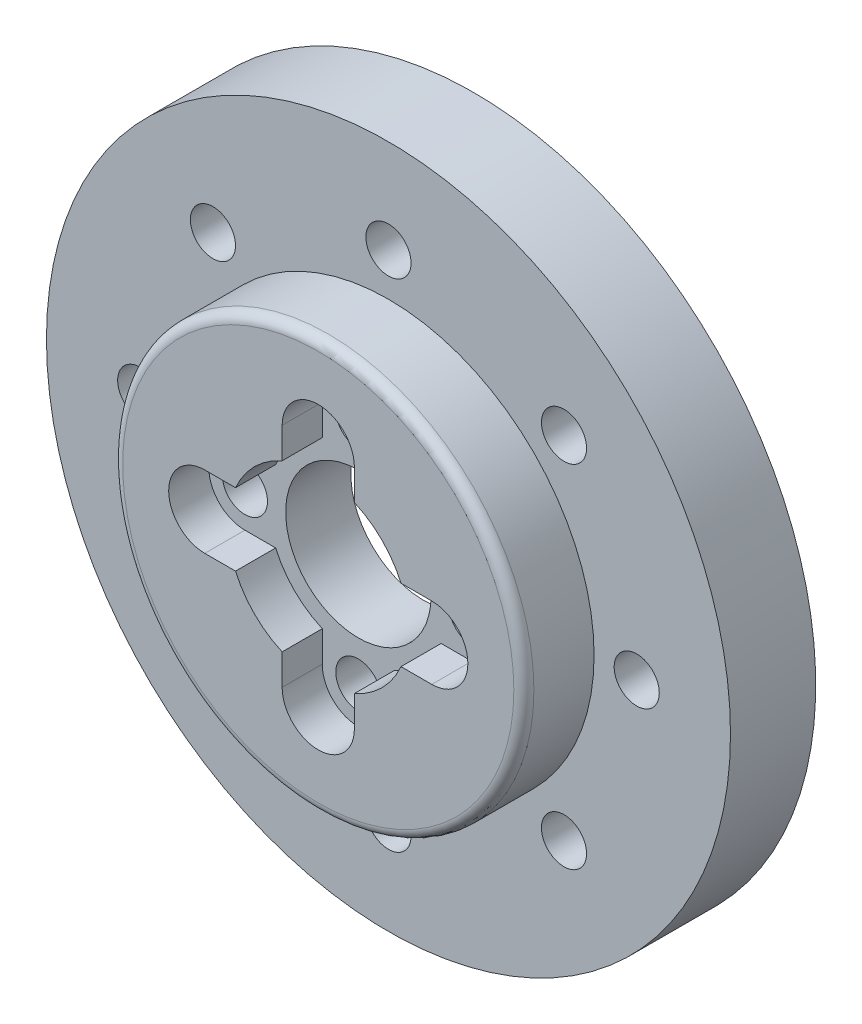
SolidWorks part; units mm, degrees
ref_plane "Front Plane" through (0, 0, 0) normal (0, 0, 1) x (1, 0, 0)
ref_plane "Top Plane" through (0, 0, 0) normal (0, 1, 0) x (1, 0, 0)
ref_plane "Right Plane" through (0, 0, 0) normal (1, 0, 0) x (0, 0, -1)
sketch "Sketch1" plane through (0, 0, 0) normal (0, 0, 1) x (1, 0, 0)
  circle A0 centre (0, 0) radius 34.1
  dimension "D1" = 68.2
extrude "Boss-Extrude1" add sketch "Sketch1" along normal mid plane 3.5
sketch "Sketch4" plane through (0, 0, 1.75) normal (0, 0, 1) x (1, 0, 0)
  circle A0 centre (0, 0) radius 28.5
  dimension "D1" = 57
extrude "Boss-Extrude2" add sketch "Sketch4" along normal blind 2
sketch "Sketch5" plane through (0, 0, -1.75) normal (0, 0, -1) x (-1, 0, 0)
  circle A0 centre (0, 0) radius 16.25
  circle A1 centre (0, 0) radius 34.1 construction
  circle A2 centre (0, 0) radius 34.1
  dimension "D1" = 32.5
extrude "Boss-Extrude3" add sketch "Sketch5" along normal blind 5
sketch "Sketch3" plane through (0, 0, 1.75) normal (0, 0, 1) x (1, 0, 0)
  circle A8 centre (0, 0) radius 11.3137 construction
  circle A9 centre (0, 11.3137) radius 2.25
  circle A11 centre (11.3137, 0) radius 2.25
  circle A13 centre (0, -11.3137) radius 2.25
  circle A15 centre (-11.3137, 0) radius 2.25
  point P21 (0, 0)
  dimension "D3" = 22.6274
  dimension "D4" = 4.5
  dimension "D5" = 4
extrude "Cut-Extrude2" cut sketch "Sketch3" against normal through all both and the other way through all
sketch "Sketch2" plane through (0, 0, 1.75) normal (0, 0, 1) x (1, 0, 0)
  circle A0 centre (0, 0) radius 7.25
  dimension "D1" = 14.5
extrude "Cut-Extrude1" cut sketch "Sketch2" along normal through all both and the other way through all
sketch "Sketch6" plane through (0, 0, 3.75) normal (0, 0, 1) x (1, 0, 0)
  circle A0 centre (0, 24.75) radius 2.25
  dimension "D1" = 4.5
  dimension "D2" = 24.75
extrude "Cut-Extrude3" cut sketch "Sketch6" against normal through all both and the other way through all
pattern_circular "CirPattern1" count 8 over 360 about axis through (0, 0, 1.75) along (0, 0, -1) of "Cut-Extrude3"
sketch "Sketch7" plane through (0, 0, 3.75) normal (0, 0, 1) x (1, 0, 0)
  circle A0 centre (0, 0) radius 20.5
  circle A5 centre (0, -11.3137) radius 2.25 construction
  circle A6 centre (11.3137, 0) radius 2.25 construction
  circle A7 centre (0, 11.3137) radius 2.25 construction
  circle A8 centre (-11.3137, 0) radius 2.25 construction
  circle A9 centre (0, 0) radius 7.25 construction
  circle A10 centre (0, -11.3137) radius 2.25
  circle A11 centre (11.3137, 0) radius 2.25
  circle A12 centre (0, 11.3137) radius 2.25
  circle A13 centre (-11.3137, 0) radius 2.25
  circle A14 centre (0, 0) radius 7.25
  dimension "D1" = 41
extrude "Boss-Extrude4" add sketch "Sketch7" along normal blind 5
sketch "Sketch8" plane through (0, 0, 1.75) normal (0, 0, 1) x (1, 0, 0)
  circle A0 centre (0, 0) radius 28.5 construction
  circle A1 centre (0, 0) radius 34.1
  circle A2 centre (0, 0) radius 34.1
  circle A3 centre (0, 0) radius 28.5
  dimension "D1" = 0
extrude "Boss-Extrude5" add sketch "Sketch8" along normal up to surface (2 mm away) up to face at (20.5, 0, 3.75)
sketch "Sketch10" plane through (0, 0, 3.75) normal (0, 0, 1) x (1, 0, 0)
  circle A0 centre (0, 0) radius 20.5 construction
  circle A1 centre (0, 0) radius 34.1
  circle A2 centre (0, 0) radius 34.1
  circle A3 centre (0, 0) radius 20.5
  dimension "D1" = 0
extrude "Cut-Extrude4" cut sketch "Sketch10" against normal blind 2
sketch "Sketch11" plane through (0, 0, 8.75) normal (0, 0, 1) x (1, 0, 0)
  line L0 (-11.3137, 3.6) -> (-8.2486, 3.6)
  line L1 (-3.6, 8.2486) -> (-3.6, 11.3137)
  line L2 (3.6, 11.3137) -> (3.6, 8.2486)
  line L3 (8.2486, 3.6) -> (11.3137, 3.6)
  line L4 (11.3137, -3.6) -> (8.2486, -3.6)
  line L5 (3.6, -8.2486) -> (3.6, -11.3137)
  line L6 (-3.6, -11.3137) -> (-3.6, -8.2486)
  line L7 (-8.2486, -3.6) -> (-11.3137, -3.6)
  circle A0 centre (-11.3137, 0) radius 2.25 construction
  circle A1 centre (0, -11.3137) radius 2.25 construction
  circle A2 centre (11.3137, 0) radius 2.25 construction
  circle A3 centre (0, 11.3137) radius 2.25 construction
  circle A4 centre (-11.3137, 0) radius 2.25 construction
  circle A5 centre (0, -11.3137) radius 2.25 construction
  circle A6 centre (11.3137, 0) radius 2.25 construction
  circle A7 centre (0, 11.3137) radius 2.25 construction
  arc A8 (-3.6, -11.3137) -> (3.6, -11.3137) centre (0, -11.3137) ccw
  arc A9 (11.3137, -3.6) -> (11.3137, 3.6) centre (11.3137, 0) ccw
  arc A10 (3.6, 11.3137) -> (-3.6, 11.3137) centre (0, 11.3137) ccw
  arc A11 (-11.3137, 3.6) -> (-11.3137, -3.6) centre (-11.3137, 0) ccw
  arc A12 (-8.2486, -3.6) -> (-3.6, -8.2486) centre (0, 0) ccw
  arc A13 (-3.6, 8.2486) -> (-8.2486, 3.6) centre (0, 0) ccw
  arc A14 (8.2486, 3.6) -> (3.6, 8.2486) centre (0, 0) ccw
  arc A15 (3.6, -8.2486) -> (8.2486, -3.6) centre (0, 0) ccw
  dimension "D1" = 7.2
  dimension "D2" = 18
extrude "Cut-Extrude5" cut sketch "Sketch11" against normal blind 4
sketch "Sketch12" plane through (0, 0, -6.75) normal (0, 0, -1) x (-1, 0, 0)
  circle A0 centre (0, 24.75) radius 4.6
  circle A1 centre (17.5009, 17.5009) radius 4.6
  circle A2 centre (24.75, 0) radius 4.6
  circle A3 centre (17.5009, -17.5009) radius 4.6
  circle A4 centre (0, -24.75) radius 4.6
  circle A5 centre (-17.5009, -17.5009) radius 4.6
  circle A6 centre (-24.75, 0) radius 4.6
  circle A7 centre (-17.5009, 17.5009) radius 4.6
  point P19 (0, 0)
  dimension "D1" = 9.2
  dimension "D2" = 8
extrude "Cut-Extrude6" cut sketch "Sketch12" against normal blind 3
fillet "Fillet2" radius 1 1 edges at (20.5, 0, 8.75)
fillet "Fillet3" radius 1 1 edges at (-16.25, 0, -1.75)
